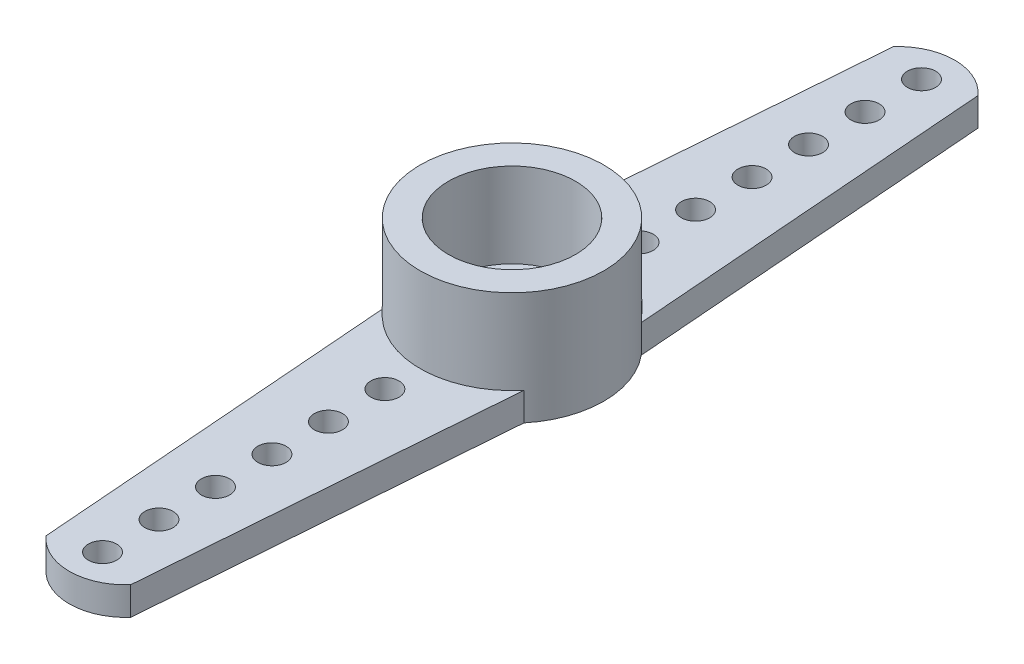
SolidWorks part; units mm, degrees
ref_plane "前视基准面" through (0, 0, 0) normal (0, 0, 1) x (1, 0, 0)
ref_plane "上视基准面" through (0, 0, 0) normal (0, 1, 0) x (1, 0, 0)
ref_plane "右视基准面" through (0, 0, 0) normal (1, 0, 0) x (0, 0, -1)
sketch "草图1" plane through (0, 0, 0) normal (0, 1, 0) x (1, 0, 0)
  line L0 (0, 15) -> (0, -15) construction
  line L1 (-1.5, 15) -> (1.5, 15) construction
  line L2 (-2.5, 2.0767) -> (2.5, 2.0767) construction
  line L3 (-1.5, 15) -> (-2.5, 2.0767)
  line L4 (1.5, 15) -> (2.5, 2.0767)
  line L5 (-5.1713, 0) -> (5.3167, 0) construction
  line L6 (1.5, -15) -> (2.5, -2.0767)
  line L7 (-1.5, -15) -> (-2.5, -2.0767)
  circle A0 centre (0, 0) radius 2.25
  circle A1 centre (0, 0) radius 3.25
  arc A2 (-1.5, 15) -> (1.5, 15) centre (0, 13.6771) cw
  arc A3 (-1.5, -15) -> (1.5, -15) centre (0, -13.6771) ccw
  circle A4 centre (0, -14.5) radius 0.5
  circle A5 centre (0, -12.5) radius 0.5
  circle A6 centre (0, -10.5) radius 0.5
  circle A7 centre (0, -8.5) radius 0.5
  circle A8 centre (0, -6.5) radius 0.5
  circle A9 centre (0, -4.5) radius 0.5
  circle A10 centre (0, 4.5) radius 0.5
  circle A11 centre (0, 6.5) radius 0.5
  circle A12 centre (0, 8.5) radius 0.5
  circle A13 centre (0, 10.5) radius 0.5
  circle A14 centre (0, 12.5) radius 0.5
  circle A15 centre (0, 14.5) radius 0.5
  dimension "D2" = 4.5
  dimension "D3" = 3
  dimension "D4" = 30
  dimension "D5" = 5
  dimension "D6" = 1
  dimension "D7" = 0.5
  dimension "D1" = 1
  dimension "D8" = 6
extrude "凸台-拉伸1" add sketch "草图1" along normal blind 4 contours A1 A0 region at (0, 0, -3.1581)
extrude "凸台-拉伸2" add sketch "草图1<3>" along normal blind 1 contours A0 region at (0, 0, 0)
sketch "草图1<3>" plane through (0, 0, 0) normal (0, 1, 0) x (1, 0, 0) same geometry as "草图1"
extrude "凸台-拉伸3" add sketch "草图1<4>" along normal blind 1 contours A2 L3 A1 L4 region at (0, 0, -15.5322)
sketch "草图1<4>" plane through (0, 0, 0) normal (0, 1, 0) x (1, 0, 0) same geometry as "草图1"
extrude "凸台-拉伸4" add sketch "草图1<5>" along normal blind 1 contours L7 A3 L6 A1 region at (0, 0, 3.3949)
sketch "草图1<5>" plane through (0, 0, 0) normal (0, 1, 0) x (1, 0, 0) same geometry as "草图1"
